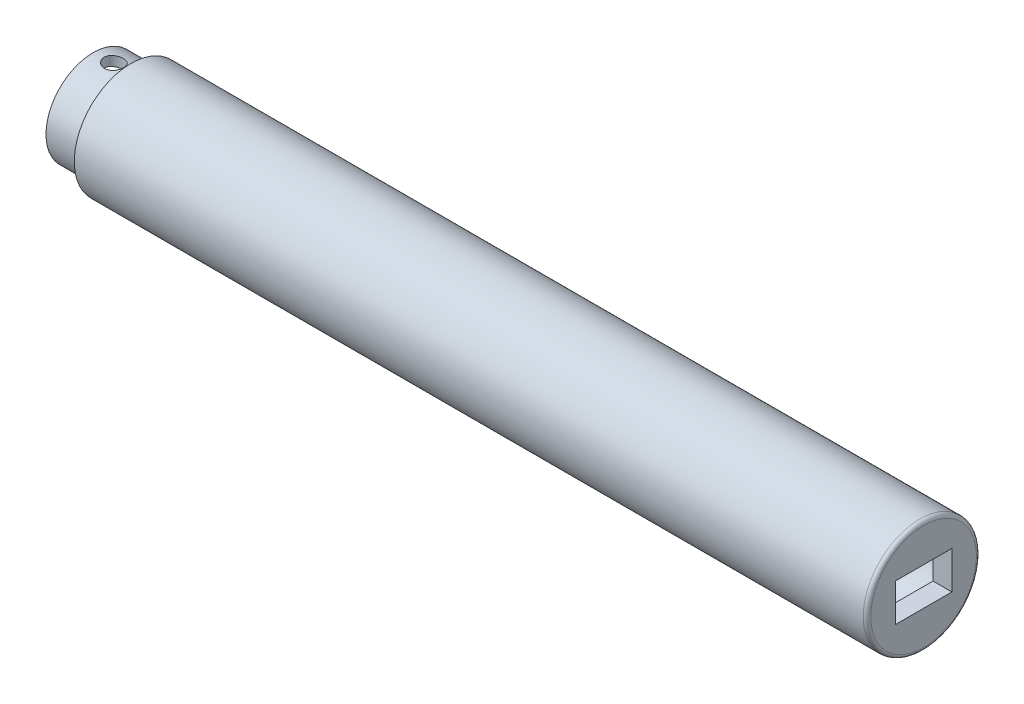
SolidWorks part; units mm, degrees
ref_plane "Plano frontal" through (0, 0, 0) normal (0, 0, 1) x (1, 0, 0)
ref_plane "Plano superior" through (0, 0, 0) normal (0, 1, 0) x (1, 0, 0)
ref_plane "Plano direito" through (0, 0, 0) normal (1, 0, 0) x (0, 0, -1)
sketch "Esboço1" plane through (0, 0, 0) normal (1, 0, 0) x (0, 0, -1)
  circle A0 centre (0, 0) radius 15
  circle A1 centre (0, 0) radius 12.5
  dimension "D1" = 30
  dimension "D2" = 25
extrude "Ressalto-extrusão1" add sketch "Esboço1" along normal blind 210 contours A1 | A0
sketch "Esboço2" plane through (0, 0, 0) normal (-1, 0, 0) x (0, 0, 1)
  line L0 (0, 15) -> (0, 0) construction
  circle A0 centre (0, 0) radius 15 construction
  circle A1 centre (0, 0) radius 10
  circle A3 centre (0, 0) radius 12.5
  dimension "D1" = 20
extrude "Ressalto-extrusão3" add sketch "Esboço2" against normal blind 15 from offset 10
sketch "Esboço4" plane through (0, 0, 0) normal (0, 1, 0) x (1, 0, 0)
  line L0 (-10, 12.5) -> (-10, -12.5) construction
  circle A0 centre (-5, 0.5) radius 2.5
  point P8 (205, 0)
  point P9 (205, 6.3168)
  point P10 (0, 0)
  dimension "D1" = 5
  dimension "D2" = 5
sketch3d "3DSketch1"
  point P0 (150.2064, 4.5345, 11.6485)
extrude "Corte-extrusão3" cut sketch "Esboço4" against normal blind 300 and the other way blind 300
sketch "Esboço9" plane through (210, 0, 0) normal (1, 0, 0) x (0, 0, -1)
  circle A0 centre (0, 0) radius 12.5
extrude "Ressalto-extrusão4" add sketch "Esboço9" against normal blind 5
fillet "Filete1" radius 1 1 edges at (210, 0, -15)
sketch "Esboço11" plane through (210, 0, 0) normal (1, 0, 0) x (0, 0, -1)
  line L1 (7.5, -5) -> (-7.5, -5)
  line L2 (7.5, -5) -> (7.5, 5)
  line L3 (7.5, 5) -> (-7.5, 5)
  line L4 (-7.5, -5) -> (-7.5, 5)
  line L5 (7.5, -5) -> (-7.5, 5) construction
  line L6 (7.5, 5) -> (-7.5, -5) construction
  point P1 (0, 0)
  dimension "D1" = 15
  dimension "D2" = 10
extrude "Corte-extrusão4" cut sketch "Esboço11" against normal blind 10
